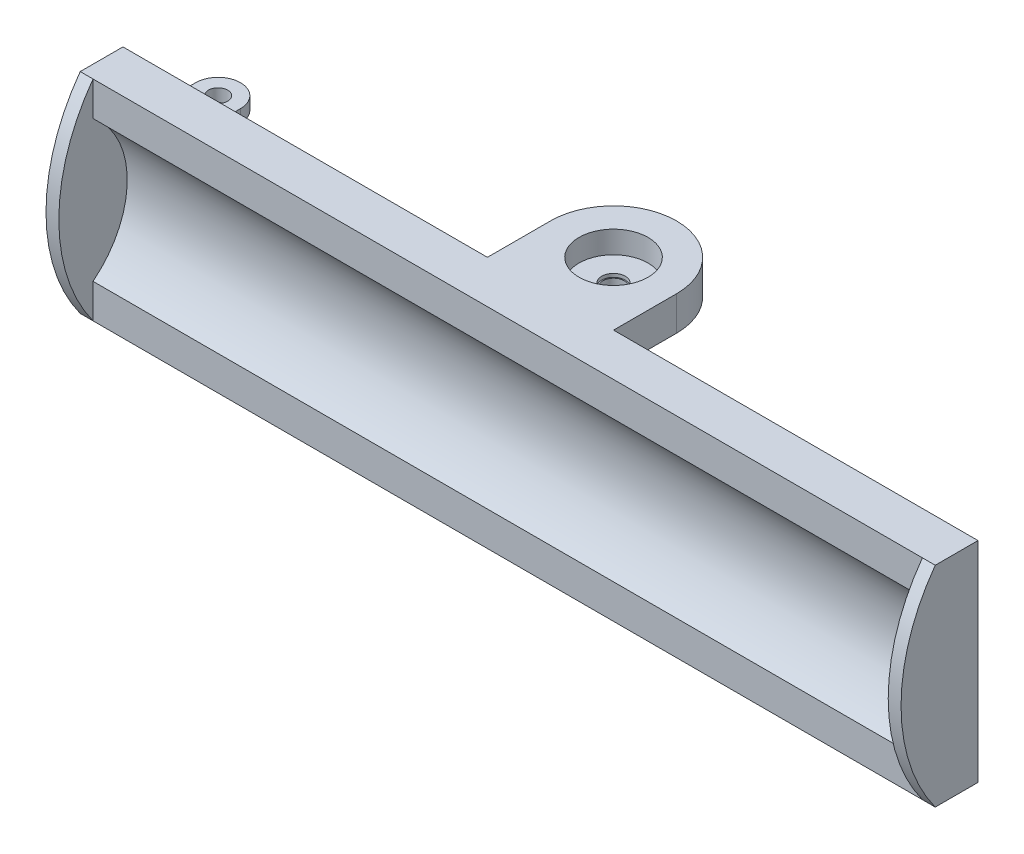
SolidWorks part; units mm, degrees
ref_plane "Front Plane" through (0, 0, 0) normal (1, 0, 0) x (0, 1, 0)
ref_plane "Top Plane" through (0, 0, 0) normal (0, 0, 1) x (0, 1, 0)
ref_plane "Right Plane" through (0, 0, 0) normal (0, 1, 0) x (-1, 0, 0)
sketch "Sketch1" plane through (0, 0, 0) normal (1, 0, 0) x (0, 1, 0)
  line L0 (-5.9881, -2) -> (7.7891, -2) construction
  line L1 (-24.5, -5) -> (24.5, -5)
  line L2 (-24.5, -5) -> (-24.5, 5)
  line L3 (-24.5, 5) -> (24.5, 5)
  line L4 (24.5, -5) -> (24.5, 5)
  line L5 (-24.5, -5) -> (24.5, 5) construction
  line L6 (-24.5, 5) -> (24.5, -5) construction
  circle A0 centre (0, 18) radius 20 construction
  circle A1 centre (0, 18) radius 21
  point P0 (0, 0)
  dimension "D3" = 40
  dimension "D4" = 3
  dimension "D1" = 49
  dimension "D2" = 10
  dimension "D5" = 1
extrude "Boss-Extrude1" add sketch "Sketch1" along normal mid plane 200 contours A1 L3 L2 L1 L4 region at (0, -23.9999, 0)
ref_plane "Midplane Width" through (0, 0, 0) normal (0, -1, 0) x (-1, 0, 0)
sketch "Sketch3" plane through (0, -24.5, 0) normal (0, -1, 0) x (1, 0, 0)
  line L0 (100, -5) -> (-100, -5) construction
  line L1 (-14.75, -19.75) -> (-14.75, -5)
  line L2 (14.75, -19.75) -> (14.75, -5)
  line L3 (-14.75, -5) -> (14.75, -5)
  circle A0 centre (0, -19.75) radius 2.75
  circle A1 centre (0, -19.75) radius 14.75
  line M4 (-100, -5) -> (100, -5)
  dimension "D2" = 12
extrude "Boss-Extrude2" add sketch "Sketch3" against normal blind 8 contours A1 A0 | A1 L1 M4 | A1 L2 L3 region at (-10.1348, -24.5, -9.6152) region at (-11.4553, -24.5, -8.2947) region at (11.4553, -24.5, -8.2947)
sketch "Sketch4" plane through (0, -24.5, 0) normal (0, -1, 0) x (-1, 0, 0)
  circle A0 centre (0, 19.75) radius 8.075
  circle A1 centre (0, 19.75) radius 2.75 construction
  circle A2 centre (0, 19.75) radius 2.75
  dimension "D1" = 16.15
extrude "Cut-Extrude1" cut sketch "Sketch4" against normal blind 5.2
sketch "Sketch5" plane through (0, -16.5, 0) normal (0, 1, 0) x (-1, 0, 0)
  circle A0 centre (0, -19.75) radius 2.5
  circle A1 centre (0, -19.75) radius 2.75 construction
  circle A2 centre (0, -19.75) radius 2.75
  dimension "D1" = 5
extrude "Boss-Extrude4" add sketch "Sketch5" against normal blind 2
mirror "Mirror1" about plane through (0, 0, 0) normal (0, -1, 0) of "Boss-Extrude4", "Boss-Extrude2", "Cut-Extrude1"
sketch "Sketch6" plane through (0, 0, 0) normal (0, -1, 0) x (-1, 0, 0)
  line L0 (0, 19.75) -> (92.5, 19.75)
  line L1 (87.25, 19.75) -> (87.25, 5)
  line L2 (14.75, 5) -> (100, 5) construction
  line L3 (97.75, 19.75) -> (97.75, 5)
  line L4 (97.75, 5) -> (87.25, 5)
  circle A0 centre (92.5, 19.75) radius 2.25
  arc A1 (97.75, 19.75) -> (87.25, 19.75) centre (92.5, 19.75) ccw
  circle A2 centre (92.5, 19.75) radius 5.25 construction
  dimension "D2" = 4.5
  dimension "D1" = 92.5
  dimension "D3" = 3
extrude "Boss-Extrude5" add sketch "Sketch6" along normal blind 3 from offset 8 contours L3 A1 A0 L1 L4 region at (-92.5, 0, -14.0126)
mirror "Mirror2" about plane through (0, 0, 0) normal (0, -1, 0) of "Boss-Extrude5"
sketch "Sketch7" plane through (-100, 0, 0) normal (-1, 0, 0) x (0, -1, 0)
  line L0 (0, 13) -> (-33.9955, 13) construction
  line L1 (-16.4924, 5) -> (16.4924, 5)
  line L5 (-16.4924, 5) -> (-24.5, 5)
  line L6 (-24.5, 5) -> (-24.5, -5)
  line L7 (-24.5, -5) -> (24.5, -5)
  line L8 (24.5, -5) -> (24.5, 5)
  line L9 (24.5, 5) -> (16.4924, 5)
  line L10 (-16.4924, 5) -> (-24.5, 5)
  line L11 (-24.5, 5) -> (-24.5, -5)
  line L12 (-24.5, -5) -> (24.5, -5)
  line L13 (24.5, -5) -> (24.5, 5)
  line L14 (24.5, 5) -> (16.4924, 5)
  arc A0 (24.5, 5) -> (-24.5, 5) centre (0, -28.5156) ccw
  arc A1 (-16.4924, 5) -> (16.4924, 5) centre (0, 18) ccw
  arc A2 (-16.4924, 5) -> (16.4924, 5) centre (0, 18) ccw
  arc M9 (16.4924, 5) -> (-16.4924, 5) centre (0, 18) cw
  line M10 (-16.4924, 5) -> (-24.5, 5)
  line M11 (-24.5, 5) -> (-24.5, -5)
  line M12 (-24.5, -5) -> (24.5, -5)
  line M13 (24.5, -5) -> (24.5, 5)
  line M14 (24.5, 5) -> (16.4924, 5)
  dimension "D2" = 8
  dimension "D1" = 0
extrude "Boss-Extrude6" add sketch "Sketch7" against normal blind 3 contours M14 M9 M10 M11 M12 M13 | L1 M9 | A0 L1 M14 M10 region at (-100, 0, 8.228) region at (-100, 0, -3.5001) region at (-100, 0, 1.7412)
mirror "Mirror3" about plane through (0, 0, 0) normal (1, 0, 0) of "Boss-Extrude6"
